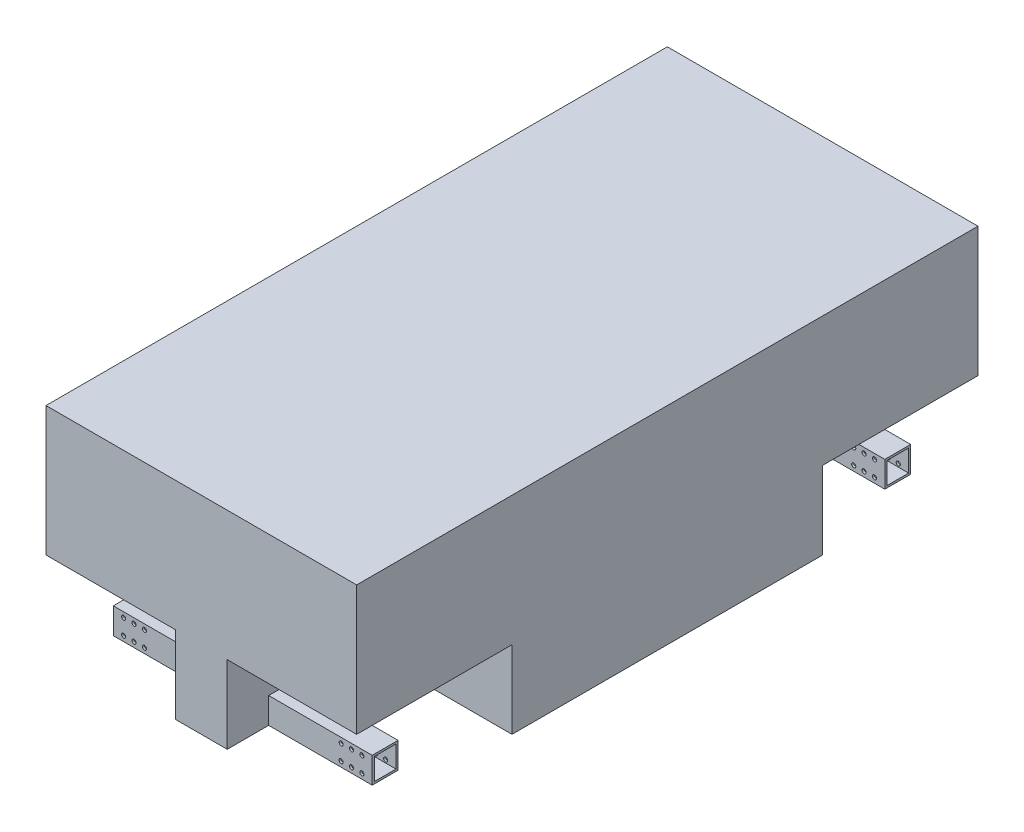
SolidWorks part; units mm, degrees
ref_plane "Front Plane" through (0, 0, 0) normal (0, 0, 1) x (1, 0, 0)
ref_plane "Top Plane" through (0, 0, 0) normal (0, 1, 0) x (1, 0, 0)
ref_plane "Right Plane" through (0, 0, 0) normal (1, 0, 0) x (0, 0, -1)
sketch "Sketch2" plane through (0, 0, 0) normal (1, 0, 0) x (0, 0, -1)
  line L1 (-300, 100) -> (300, 100)
  line L2 (-300, 100) -> (-300, -100)
  line L3 (-300, -100) -> (300, -100)
  line L4 (300, 100) -> (300, -100)
  line L5 (-300, 100) -> (300, -100) construction
  line L6 (-300, -100) -> (300, 100) construction
  point P0 (0, 0)
  dimension "D1" = 600
  dimension "D2" = 200
extrude "Boss-Extrude1" add sketch "Sketch2" along normal blind 150 and the other way blind 150
sketch "Sketch3" plane through (150, 0, 0) normal (1, 0, 0) x (0, 0, -1)
  line L1 (-300, -100) -> (-150, -100)
  line L2 (-300, -100) -> (-300, -25)
  line L3 (-300, -25) -> (-150, -25)
  line L4 (-150, -100) -> (-150, -25)
  line L5 (300, -100) -> (150, -100)
  line L6 (300, -100) -> (300, -25)
  line L7 (300, -25) -> (150, -25)
  line L8 (150, -100) -> (150, -25)
  dimension "D1" = 150
  dimension "D2" = 150
  dimension "D3" = 75
  dimension "D4" = 75
extrude "Cut-Extrude1" cut sketch "Sketch3" against normal blind 125
mirror "Mirror1" about plane through (0, 0, 0) normal (1, 0, 0) of "Cut-Extrude1"
sketch "Sketch4" plane through (25, 0, 0) normal (1, 0, 0) x (0, 0, -1)
  line L0 (-300, -100) -> (-150, -100) construction
  line L1 (-260, -75) -> (-235, -75)
  line L2 (-260, -75) -> (-260, -100)
  line L3 (-260, -100) -> (-235, -100)
  line L4 (-235, -75) -> (-235, -100)
  line L5 (-300, -25) -> (-300, -100) construction
  line L6 (-258, -77) -> (-258, -98)
  line L7 (-258, -98) -> (-237, -98)
  line L8 (-237, -77) -> (-237, -98)
  line L9 (-258, -77) -> (-237, -77)
  dimension "D1" = 25
  dimension "D2" = 25
  dimension "D3" = 0
  dimension "D4" = 40
  dimension "D5" = 2
extrude "Boss-Extrude2" add sketch "Sketch4" along normal blind 100
sketch "Sketch5" plane through (0, 0, 260) normal (0, 0, 1) x (1, 0, 0)
  line L0 (125, -75) -> (25, -75) construction
  line L1 (125, -100) -> (25, -100) construction
  line L2 (125, -75) -> (125, -100) construction
  circle A0 centre (115, -80) radius 2
  circle A1 centre (105, -80) radius 2
  circle A2 centre (95, -80) radius 2
  circle A3 centre (115, -95) radius 2
  circle A4 centre (105, -95) radius 2
  circle A5 centre (95, -95) radius 2
  dimension "D1" = 5
  dimension "D2" = 5
  dimension "D3" = 5
  dimension "D4" = 5
  dimension "D5" = 5
  dimension "D6" = 5
  dimension "D7" = 10
  dimension "D8" = 10
  dimension "D9" = 10
  dimension "D10" = 10
  dimension "D11" = 10
  dimension "D12" = 10
extrude "Cut-Extrude2" cut sketch "Sketch5" against normal blind 25
mirror "Mirror2" about plane through (0, 0, 0) normal (1, 0, 0) of "Cut-Extrude2", "Boss-Extrude2"
mirror "Mirror3" about plane through (0, 0, 0) normal (0, 0, 1) of "Mirror2"
